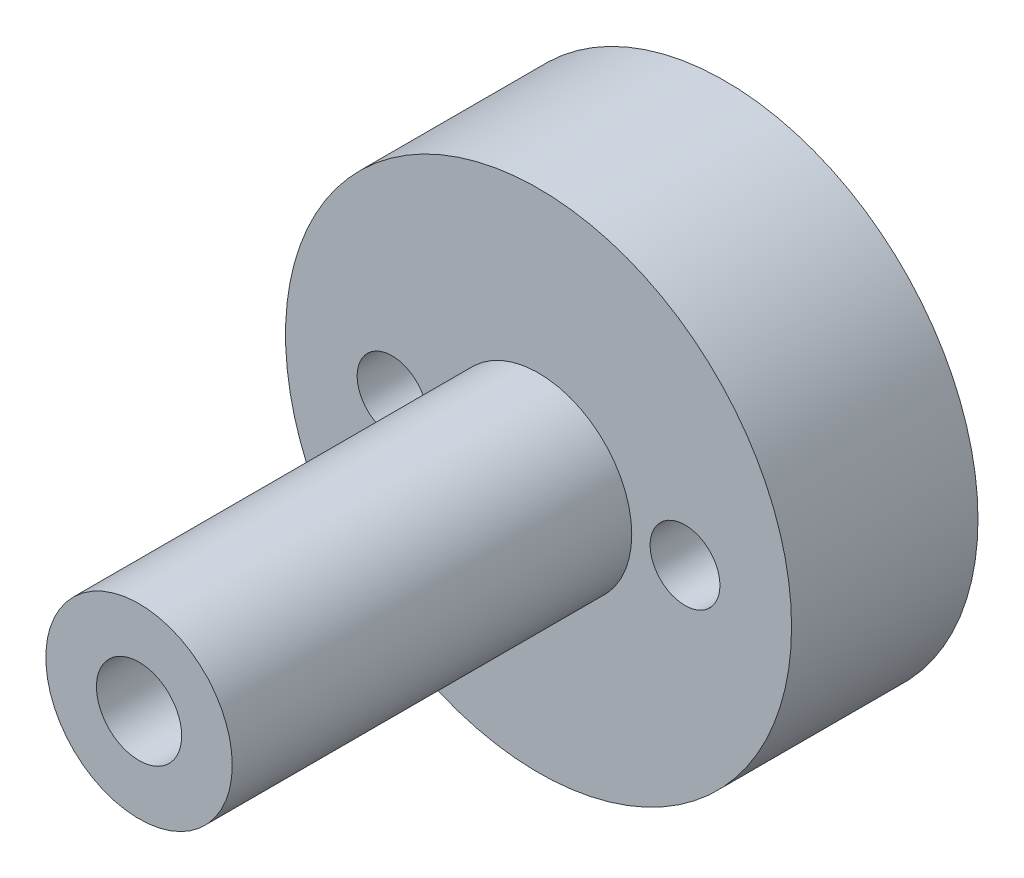
SolidWorks part; units mm, degrees
ref_plane "Front Plane" through (0, 0, 0) normal (0, 0, 1) x (1, 0, 0)
ref_plane "Top Plane" through (0, 0, 0) normal (0, 1, 0) x (1, 0, 0)
ref_plane "Right Plane" through (0, 0, 0) normal (1, 0, 0) x (0, 0, -1)
sketch "Sketch1" plane through (0, 0, 0) normal (0, 0, 1) x (1, 0, 0)
  circle A0 centre (0, 0) radius 7.6
  circle A1 centre (0, 0) radius 9.5
  dimension "D1" = 15.2
  dimension "D2" = 19
extrude "Boss-Extrude1" add sketch "Sketch1" along normal blind 5
sketch "Sketch2" plane through (0, 0, 5) normal (0, 0, 1) x (1, 0, 0)
  circle A0 centre (0, 0) radius 9.5 construction
  circle A1 centre (0, 0) radius 9.5
  circle A2 centre (0, 0) radius 1.31
  dimension "D1" = 2.62
extrude "Boss-Extrude2" add sketch "Sketch2" along normal blind 2
sketch "Sketch3" plane through (0, 0, 7) normal (0, 0, 1) x (1, 0, 0)
  circle A0 centre (-5.5, 0) radius 1.31
  circle A1 centre (5.5, 0) radius 1.31
  circle A2 centre (0, 0) radius 1.31 construction
  circle A3 centre (0, 0) radius 1.6
  circle A4 centre (0, 0) radius 3.5
  dimension "D1" = 5.5
  dimension "D3" = 3.2
  dimension "D4" = 7
  dimension "D2" = 5.5
extrude "Boss-Extrude3" add sketch "Sketch3" along normal blind 15 contours A4 A3 region at (-3.401, 0, 7)
extrude "Cut-Extrude1" cut sketch "Sketch3<3>" against normal through all both and the other way through all contours A0 | A1 region at (-5.5, 0, 7)
sketch "Sketch3<3>" plane through (0, 0, 7) normal (0, 0, 1) x (1, 0, 0) same geometry as "Sketch3"
